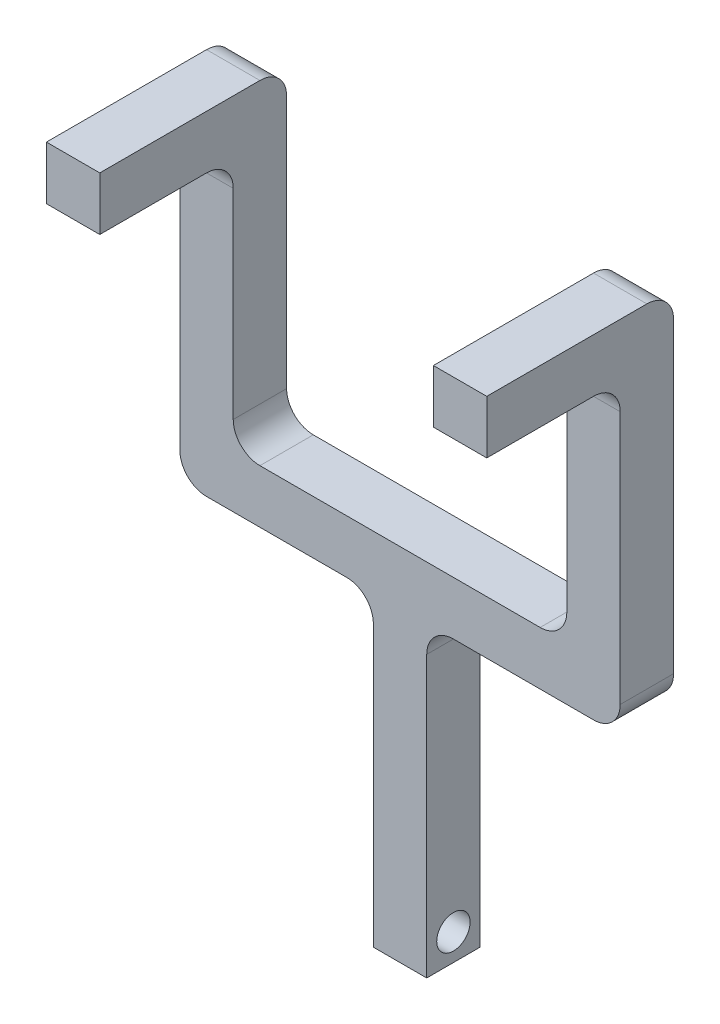
SolidWorks part; units mm, degrees
ref_plane "Plan de face" through (0, 0, 0) normal (0, 0, 1) x (1, 0, 0)
ref_plane "Plan de dessus" through (0, 0, 0) normal (0, 1, 0) x (1, 0, 0)
ref_plane "Plan de droite" through (0, 0, 0) normal (1, 0, 0) x (0, 0, -1)
sketch "Esquisse1" plane through (0, 0, 0) normal (0, 0, 1) x (1, 0, 0)
  line L0 (29, 0) -> (29, 46)
  line L1 (0, 0) -> (66, 0) construction
  line L2 (0, 0) -> (0, 100) construction
  line L3 (0, 100) -> (66, 100) construction
  line L4 (66, 0) -> (66, 100) construction
  line L5 (29, 46) -> (0, 46)
  line L6 (0, 46) -> (0, 100)
  line L7 (0, 100) -> (8, 100)
  line L8 (8, 100) -> (8, 54)
  line L9 (8, 54) -> (58, 54)
  line L10 (58, 54) -> (58, 100)
  line L11 (58, 100) -> (66, 100)
  line L12 (66, 100) -> (66, 46)
  line L13 (66, 46) -> (37, 46)
  line L14 (37, 46) -> (37, 0)
  line L15 (37, 0) -> (29, 0)
  dimension "D1" = 66
  dimension "D2" = 100
  dimension "D3" = 8
  dimension "D4" = 8
  dimension "D5" = 8
  dimension "D6" = 8
extrude "Boss.-Extru.1" add sketch "Esquisse1" along normal blind 8
sketch "Esquisse2" plane through (0, 0, 8) normal (0, 0, 1) x (1, 0, 0)
  line L0 (8, 54) -> (8, 100) construction
  line L1 (0, 100) -> (0, 46) construction
  line L2 (8, 100) -> (0, 100) construction
  line L3 (8, 92) -> (8, 100)
  line L4 (0, 100) -> (0, 92)
  line L5 (8, 100) -> (0, 100)
  line L6 (0, 92) -> (8, 92)
  line L7 (66, 46) -> (66, 100) construction
  line L8 (58, 100) -> (58, 54) construction
  line L9 (66, 100) -> (58, 100) construction
  line L10 (66, 92) -> (66, 100)
  line L11 (58, 100) -> (58, 92)
  line L12 (66, 100) -> (58, 100)
  line L13 (58, 92) -> (66, 92)
  dimension "D1" = 8
  dimension "D2" = 8
extrude "Boss.-Extru.2" add sketch "Esquisse2" along normal blind 20
sketch "Esquisse3" plane through (29, 0, 0) normal (-1, 0, 0) x (0, 0, 1)
  line L2 (8, 0) -> (0, 0) construction
  line L3 (0, 46) -> (0, 0) construction
  circle A0 centre (4, 4) radius 2.5
  dimension "D1" = 5
  dimension "D3" = 4
hole_wizard "Diamètre du perçage Ø5.0 (5)1" positions "Esquisse4" profile "Esquisse6" hole size "Ø5.0" standard "ISO"
sketch "Esquisse4" plane through (29, 0, 0) normal (-1, 0, 0) x (0, 0, 1)
  point P0 (4, 4)
sketch "Esquisse6" plane through (29, 4, 4) normal (0, 1, 0) x (0, 0, 1)
  line L0 (0, 0) -> (0, 9.5022)
  line L1 (0, 9.5022) -> (2.5, 8)
  line L2 (2.5, 8) -> (2.5, 0)
  line L5 (2.5, 0) -> (0, 0)
  line L10 (0, 9.5022) -> (-2.5, 8) construction
  line L11 (0, -6.35) -> (0, 107.95) construction
  dimension "Diamètre du perçage" = 5
  dimension "Profondeur du perçage" = 8
  dimension "Angle de pointe" = 118
fillet "Congé1" radius 4 10 edges at (66, 46, 4) (37, 46, 4) (62, 100, 0) (58, 54, 4) (8, 54, 4) (4, 100, 0) (0, 46, 4) (29, 46, 4) (62, 92, 8) (4, 92, 8)
equation "\"long_tot\" = 100"
equation "\"espac_sub_arms\" = 50"
equation "\"épaiss_cadre\"= 8"
equation "\"long_protub\"= 20"
equation "\"D1@Esquisse1\"=\"espac_sub_arms\"+\"épaiss_cadre\"*2"
equation "\"D2@Esquisse1\"=\"long_tot\""
equation "\"D3@Esquisse1\"=\"épaiss_cadre\""
equation "\"D4@Esquisse1\"=\"épaiss_cadre\""
equation "\"D5@Esquisse1\"=\"épaiss_cadre\""
equation "\"D6@Esquisse1\"=\"épaiss_cadre\""
equation "\"D1@Boss.-Extru.1\"=\"épaiss_cadre\""
equation "\"rayon_conge\"= 3"
equation "\"D1@Esquisse2\"=\"épaiss_cadre\""
equation "\"D2@Esquisse2\"=\"épaiss_cadre\""
equation "\"D1@Boss.-Extru.2\"=\"long_protub\""
equation "\"diam_axe\"= 5"
equation "\"D1@Esquisse3\"=\"diam_axe\""
equation "\"D2@Esquisse3\"=\"épaiss_cadre\"/2"
equation "\"D3@Esquisse3\"=\"D2@Esquisse3\""
